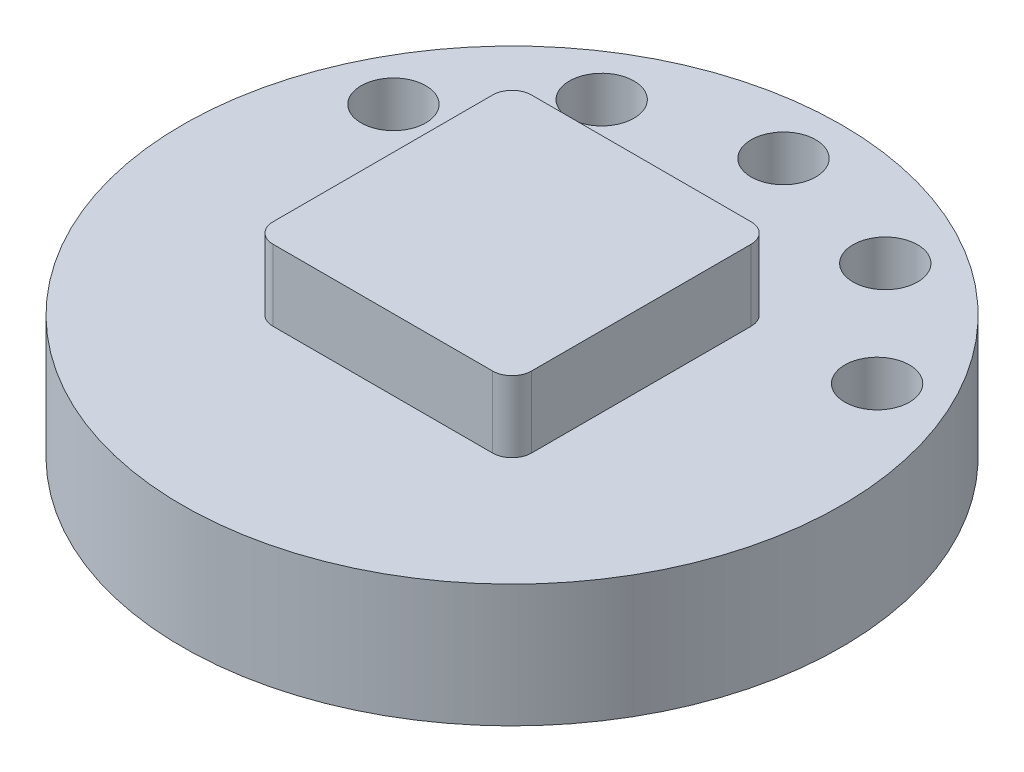
SolidWorks part; units mm, degrees
ref_plane "Ebene vorne" through (0, 0, 0) normal (0, 0, 1) x (1, 0, 0)
ref_plane "Ebene oben" through (0, 0, 0) normal (0, 1, 0) x (1, 0, 0)
ref_plane "Ebene rechts" through (0, 0, 0) normal (1, 0, 0) x (0, 0, -1)
sketch "Skizze1" plane through (0, 0, 0) normal (0, 1, 0) x (1, 0, 0)
  line L0 (0, 9.5538) -> (0, -6.6268) construction
  line L1 (-8.6595, 0) -> (6.5384, 0) construction
  line L2 (3.7422, 1.9068) -> (0, 0) construction
  line L3 (2.1945, 3.5811) -> (0, 0) construction
  circle A0 centre (0, 0) radius 5.1
  circle A1 centre (0, 0) radius 4.2 construction
  circle A2 centre (0, 4.2) radius 0.5
  circle A3 centre (2.1945, 3.5811) radius 0.5
  circle A4 centre (3.7422, 1.9068) radius 0.5
  circle A5 centre (-3.7422, 1.9068) radius 0.5
  circle A6 centre (-2.1945, 3.5811) radius 0.5
  dimension "D1" = 10.2
  dimension "D2" = 8.4
  dimension "D3" = 27
  dimension "D4" = 1
extrude "Aufsatz-Linear austragen1" add sketch "Skizze1" along normal blind 1.9
sketch "Skizze2" plane through (0, 1.9, 0) normal (0, 1, 0) x (1, 0, 0)
  line L1 (-2, -2) -> (2, -2)
  line L2 (-2, -2) -> (-2, 2)
  line L3 (-2, 2) -> (2, 2)
  line L4 (2, -2) -> (2, 2)
  line L5 (-2, -2) -> (2, 2) construction
  line L6 (-2, 2) -> (2, -2) construction
  point P0 (0, 0)
  dimension "D1" = 4
  dimension "D2" = 4
extrude "Aufsatz-Linear austragen2" add sketch "Skizze2" along normal blind 1.1
ref_axis "Achse1" through (0, -0.15, 0) along (0, 1, 0)
fillet "Verrundung1" radius 0.3 4 edges at (-2, 2.45, 2) (2, 2.45, 2) (2, 2.45, -2) (-2, 2.45, -2)
